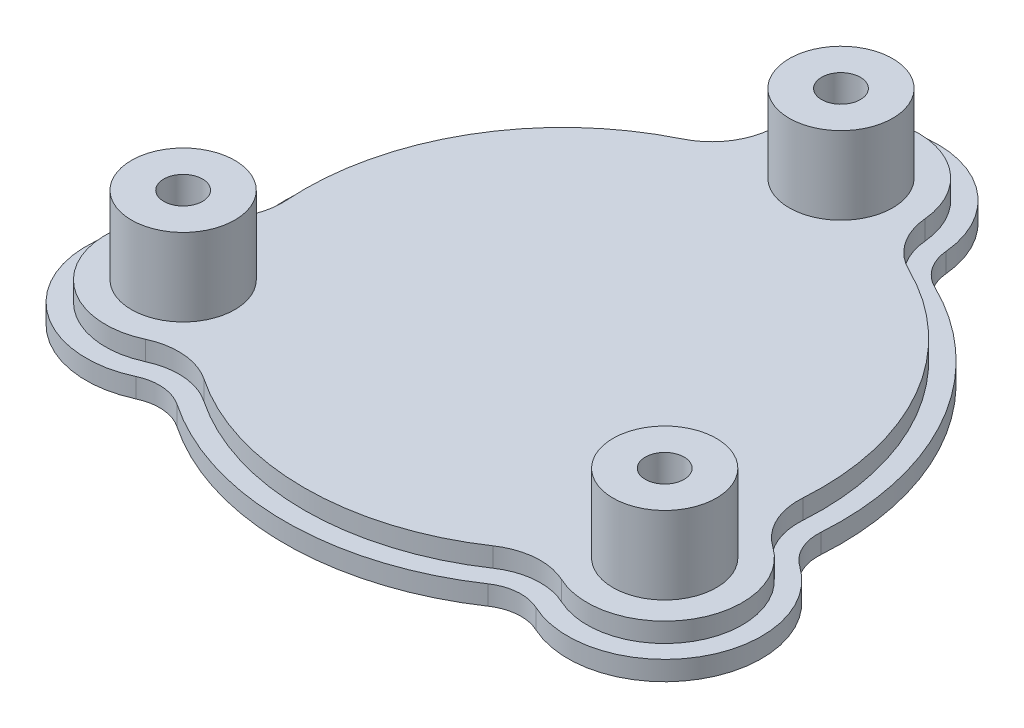
SolidWorks part; units mm, degrees
ref_plane "Front Plane" through (0, 0, 0) normal (0, 0, 1) x (1, 0, 0)
ref_plane "Top Plane" through (0, 0, 0) normal (0, 1, 0) x (1, 0, 0)
ref_plane "Right Plane" through (0, 0, 0) normal (1, 0, 0) x (0, 0, -1)
sketch "Sketch1" plane through (0, 0, 0) normal (0, 1, 0) x (1, 0, 0)
  arc A0 (-18.8462, 38.65) -> (-42.895, -3.0038) centre (0, 0) ccw
  arc A1 (14.9415, 44.324) -> (-14.9415, 44.324) centre (0, 43) ccw
  circle A2 centre (0, 43) radius 6
  circle A3 centre (0, 43) radius 3
  arc A4 (30.915, -35.1017) -> (45.8564, -9.2223) centre (37.2391, -21.5) ccw
  circle A5 centre (37.2391, -21.5) radius 6
  circle A6 centre (37.2391, -21.5) radius 3
  arc A7 (-45.8564, -9.2223) -> (-30.915, -35.1017) centre (-37.2391, -21.5) ccw
  circle A8 centre (-37.2391, -21.5) radius 6
  circle A9 centre (-37.2391, -21.5) radius 3
  arc A10 (-24.0488, -35.6462) -> (-30.915, -35.1017) centre (-27.9637, -41.4491) ccw
  arc A11 (-45.8564, -9.2223) -> (-42.895, -3.0038) centre (-49.8779, -3.4927) ccw
  arc A12 (14.9415, 44.324) -> (18.8462, 38.65) centre (21.9141, 44.9419) ccw
  arc A13 (-18.8462, 38.65) -> (-14.9415, 44.324) centre (-21.9141, 44.9419) ccw
  arc A14 (30.915, -35.1017) -> (24.0488, -35.6462) centre (27.9637, -41.4491) ccw
  arc A15 (42.895, -3.0038) -> (45.8564, -9.2223) centre (49.8779, -3.4927) ccw
  arc A17 (-24.0488, -35.6462) -> (24.0488, -35.6462) centre (0, 0) ccw
  arc A21 (42.895, -3.0038) -> (18.8462, 38.65) centre (0, 0) ccw
  point P18 (0, 0)
  point P20 (0, 0)
  point P30 (0, 0)
  dimension "D1" = 86
  dimension "D2" = 30
  dimension "D3" = 12
  dimension "D4" = 6
  dimension "D6" = 14
  dimension "D7" = 14
  dimension "D5" = 3
  dimension "D8" = 3
extrude "Boss-Extrude1" add sketch "Sketch1" along normal blind 3 contours A15 A21 A12 A1 A13 A0 A11 A7 A10 A17 A14 A4 A2 A5 A8 region at (0, 0, 0)
sketch "Sketch2" plane through (0, 3, 0) normal (0, 1, 0) x (1, 0, 0)
  circle A12 centre (-37.2391, -21.5) radius 6
  circle A13 centre (37.2391, -21.5) radius 6
  circle A14 centre (0, 43) radius 6
  arc A24 (39.9023, -2.7942) -> (44.133, -11.6779) centre (49.8779, -3.4927) ccw
  arc A25 (39.9023, -2.7942) -> (17.5313, 35.9535) centre (0, 0) ccw
  arc A26 (11.9532, 44.0592) -> (17.5313, 35.9535) centre (21.9141, 44.9419) ccw
  arc A27 (11.9532, 44.0592) -> (-11.9532, 44.0592) centre (0, 43) ccw
  arc A28 (-17.5313, 35.9535) -> (-11.9532, 44.0592) centre (-21.9141, 44.9419) ccw
  arc A29 (-17.5313, 35.9535) -> (-39.9023, -2.7942) centre (0, 0) ccw
  arc A30 (-44.133, -11.6779) -> (-39.9023, -2.7942) centre (-49.8779, -3.4927) ccw
  arc A31 (-44.133, -11.6779) -> (-32.1798, -32.3813) centre (-37.2391, -21.5) ccw
  arc A32 (-22.371, -33.1593) -> (-32.1798, -32.3813) centre (-27.9637, -41.4491) ccw
  arc A33 (-22.371, -33.1593) -> (22.371, -33.1593) centre (0, 0) ccw
  arc A34 (32.1798, -32.3813) -> (22.371, -33.1593) centre (27.9637, -41.4491) ccw
  arc A35 (32.1798, -32.3813) -> (44.133, -11.6779) centre (37.2391, -21.5) ccw
  arc A36 (39.9023, -2.7942) -> (44.133, -11.6779) centre (49.8779, -3.4927) ccw
  arc A37 (39.9023, -2.7942) -> (17.5313, 35.9535) centre (0, 0) ccw
  arc A38 (11.9532, 44.0592) -> (17.5313, 35.9535) centre (21.9141, 44.9419) ccw
  arc A39 (11.9532, 44.0592) -> (-11.9532, 44.0592) centre (0, 43) ccw
  arc A40 (-17.5313, 35.9535) -> (-11.9532, 44.0592) centre (-21.9141, 44.9419) ccw
  arc A41 (-17.5313, 35.9535) -> (-39.9023, -2.7942) centre (0, 0) ccw
  arc A42 (-44.133, -11.6779) -> (-39.9023, -2.7942) centre (-49.8779, -3.4927) ccw
  arc A43 (-44.133, -11.6779) -> (-32.1798, -32.3813) centre (-37.2391, -21.5) ccw
  arc A44 (-22.371, -33.1593) -> (-32.1798, -32.3813) centre (-27.9637, -41.4491) ccw
  arc A45 (-22.371, -33.1593) -> (22.371, -33.1593) centre (0, 0) ccw
  arc A46 (32.1798, -32.3813) -> (22.371, -33.1593) centre (27.9637, -41.4491) ccw
  arc A47 (32.1798, -32.3813) -> (44.133, -11.6779) centre (37.2391, -21.5) ccw
  dimension "D2" = 12
  dimension "D3" = 12
  dimension "D4" = 12
  dimension "D1" = 3
extrude "Boss-Extrude2" add sketch "Sketch2" along normal blind 3
sketch "Sketch3" plane through (0, 6, 0) normal (0, 1, 0) x (1, 0, 0)
  circle A0 centre (0, 43) radius 8
  circle A1 centre (37.2391, -21.5) radius 8
  circle A2 centre (-37.2391, -21.5) radius 8
  circle A4 centre (0, 43) radius 6
  circle A5 centre (37.2391, -21.5) radius 6
  circle A6 centre (-37.2391, -21.5) radius 6
  circle A8 centre (0, 43) radius 3
  circle A9 centre (37.2391, -21.5) radius 3
  circle A10 centre (-37.2391, -21.5) radius 3
  point P5 (0, 0)
  point P10 (0, 0)
  point P15 (0, 0)
  point P21 (0, 0)
  circle M1 centre (37.2391, -21.5) radius 6
  circle M14 centre (-37.2391, -21.5) radius 6
  circle M15 centre (0, 43) radius 6
  dimension "D1" = 16
  dimension "D3" = 3
  dimension "D4" = 12
  dimension "D5" = 6
  dimension "D2" = 3
  dimension "D6" = 3
extrude "Boss-Extrude3" add sketch "Sketch3" along normal blind 6 contours A2 M14 | A0 M15 | A1 M1 region at (-7.7737, 6, -43) region at (29.4654, 6, 21.5) region at (-45.0128, 6, 21.5)
extrude "Boss-Extrude4" add sketch "Sketch3<4>" along normal blind 6 from surface contours A2 M14 | A10 M14 | A8 M15 | A0 M15 | A1 M1 | A9 M1 region at (-7.7737, 6, -43) region at (29.4654, 6, 21.5) region at (-45.0128, 6, 21.5) region at (-5.8303, 6, -43) region at (31.4088, 6, 21.5) region at (-43.0694, 6, 21.5) starting at face at (-37.2391, 12, 27.5)
sketch "Sketch3<4>" plane through (0, 6, 0) normal (0, 1, 0) x (1, 0, 0) same geometry as "Sketch3"
